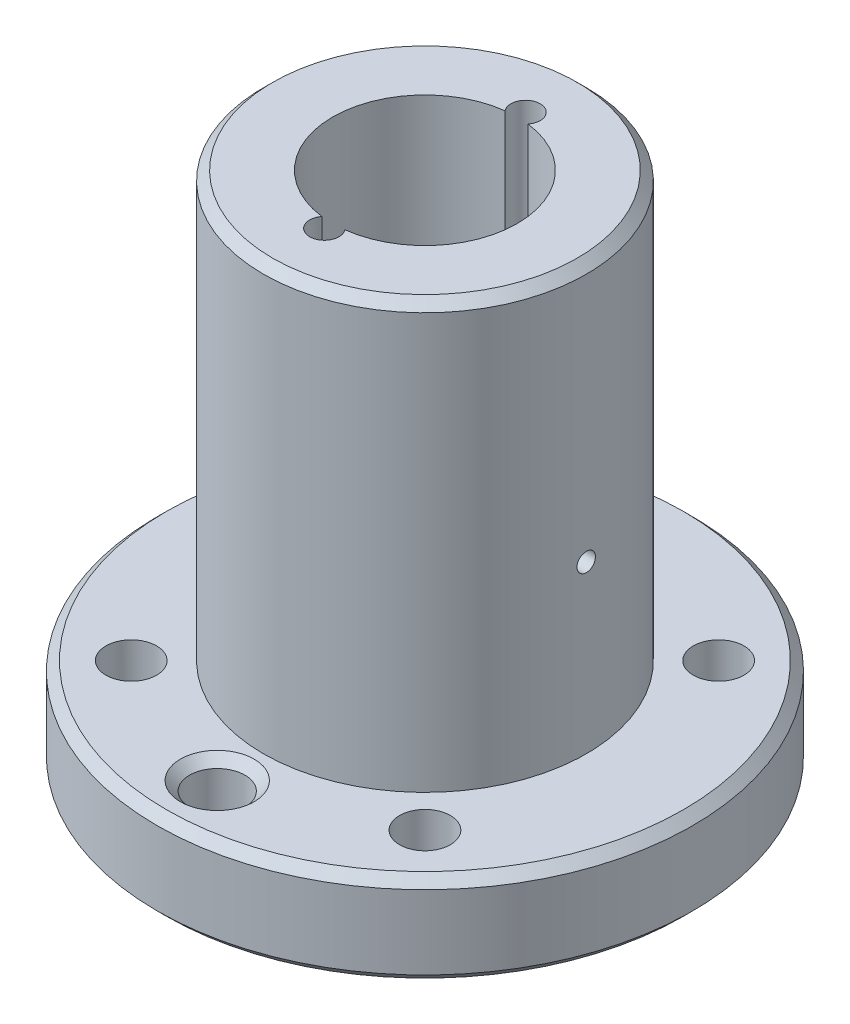
SolidWorks part; units mm, degrees
ref_plane "前视基准面" through (0, 0, 0) normal (0, 0, 1) x (1, 0, 0)
ref_plane "上视基准面" through (0, 0, 0) normal (0, 1, 0) x (1, 0, 0)
ref_plane "右视基准面" through (0, 0, 0) normal (1, 0, 0) x (0, 0, -1)
sketch "草图1" plane through (0, 0, 0) normal (0, 1, 0) x (1, 0, 0)
  circle A0 centre (0, 0) radius 29
  dimension "D1" = 58
extrude "凸台-拉伸1" add sketch "草图1" along normal blind 10 contours A0
sketch "草图2" plane through (0, 0, 0) normal (0, 1, 0) x (1, 0, 0)
  circle A0 centre (0, 0) radius 17.5
  dimension "D1" = 35
extrude "凸台-拉伸2" add sketch "草图2" along normal blind 56
sketch "草图3" plane through (0, 0, 0) normal (0, 1, 0) x (1, 0, 0)
  line L0 (-20.6924, 0) -> (25.4755, 0) construction
  line L1 (0, -13.4656) -> (0, 18.3528) construction
  circle A0 centre (0, 0) radius 10
  circle A1 centre (0, -10.9) radius 1.585
  circle A2 centre (0, 10.9) radius 1.585
  point P9 (0, -9.315)
  dimension "D1" = 20
  dimension "D2" = 9.315
  dimension "D3" = 10.9
extrude "切除-拉伸1" cut sketch "草图3" along normal up to surface (56 mm away) contours A0 up to face at (0, 56, 17.5)
sketch "草图4" plane through (0, 0, 0) normal (0, -1, 0) x (1, 0, 0)
  line L0 (-41.1768, 0) -> (51.7309, 0) construction
  line L1 (0, 31.5584) -> (0, -31.9744) construction
  line L2 (-15.9099, 15.9099) -> (0, 0) construction
  circle A0 centre (0, 0) radius 22.5 construction
  circle A1 centre (-15.9099, 15.9099) radius 4.75
  circle A2 centre (-15.9099, 15.9099) radius 2.75
  circle A3 centre (15.9099, 15.9099) radius 2.75
  circle A4 centre (15.9099, 15.9099) radius 4.75
  circle A5 centre (15.9099, -15.9099) radius 2.75
  circle A6 centre (15.9099, -15.9099) radius 4.75
  circle A7 centre (-15.9099, -15.9099) radius 2.75
  circle A8 centre (-15.9099, -15.9099) radius 4.75
  circle A9 centre (0, 22.5) radius 3
  dimension "D1" = 45
  dimension "D3" = 9.5
  dimension "D4" = 5.5
  dimension "D5" = 6
  dimension "D2" = 45
extrude "切除-拉伸2" cut sketch "草图4" against normal up to next contours A2 | A7 | A5 | A3 | A9 region at (-15.9099, 0, 15.9099) region at (15.9099, 0, 15.9099) region at (15.9099, 0, -15.9099) region at (-15.9099, 0, -15.9099) region at (0, 0, 22.5)
extrude "切除-拉伸3" cut sketch "草图4<4>" against normal blind 5.4 contours A1 A2 | A4 A3 | A6 A5 | A8 A7 region at (-20.5256, 0, 15.9099) region at (11.2943, 0, 15.9099) region at (11.2943, 0, -15.9099) region at (-20.5256, 0, -15.9099)
sketch "草图4<4>" plane through (0, 0, 0) normal (0, -1, 0) x (1, 0, 0) same geometry as "草图4"
extrude "切除-拉伸4" cut sketch "草图3<3>" along normal up to next contours A0 A1 | A2 A0 region at (0, 0, -11.1112) region at (0, 0, 11.1112)
sketch "草图3<3>" plane through (0, 0, 0) normal (0, 1, 0) x (1, 0, 0) same geometry as "草图3"
ref_plane "基准面1" through (0, 28, 0) normal (0, 1, 0) x (1, 0, 0)
ref_plane "基准面2" through (0, 24, 0) normal (0, 1, 0) x (1, 0, 0)
sketch "草图5" plane through (0, 24, 0) normal (0, 1, 0) x (1, 0, 0)
  line L0 (-36.4872, 0) -> (42.7209, 0) construction
  line L1 (0, 27.7943) -> (0, -30.5394) construction
  line L2 (15.9099, 15.9099) -> (-15.9099, -15.9099) construction
  line L3 (-15.9099, 15.9099) -> (15.9099, -15.9099) construction
  circle A0 centre (0, 0) radius 17.5 construction
  circle A1 centre (0, 0) radius 17.5 construction
  circle A2 centre (0, 0) radius 17.5 construction
  point P9 (-12.3744, 12.3744)
  point P23 (12.3744, 12.3744)
  point P26 (-12.3744, -12.3744)
  point P27 (12.3744, -12.3744)
sketch "草图6" plane through (0, 28, 0) normal (0, 1, 0) x (1, 0, 0)
  line L0 (-33.9389, 0) -> (36.0687, 0) construction
  line L2 (-36.4872, 0) -> (42.7209, 0) construction
  circle A0 centre (0, 0) radius 17.5 construction
  circle A1 centre (0, 0) radius 17.5 construction
  point P3 (-17.5, 0)
  point P4 (17.5, 0)
sketch "草图9" plane through (0, 0, 0) normal (1, 0, 0) x (0, 0, -1)
  circle A0 centre (0, 28) radius 1
  dimension "D1" = 2
extrude "切除-拉伸5" cut sketch "草图9" against normal through all both and the other way through all
sketch "草图11" plane through (0, 0, 0) normal (0, 1, 0) x (1, 0, 0)
  line L0 (15.9099, 15.9099) -> (-15.9099, -15.9099) construction
  line L1 (19.2687, -12.5511) -> (15.2686, -8.5511)
  line L2 (-36.4872, 0) -> (42.7209, 0) construction
  line L3 (12.5511, -19.2687) -> (8.5511, -15.2686)
  line L4 (12.5511, -19.2687) -> (19.2687, -12.5511)
  line L5 (0, -33.6084) -> (0, 31.7942) construction
  line L6 (-39.5862, 0) -> (54.9544, 0) construction
  line L7 (-19.2687, -12.5511) -> (-15.2686, -8.5511)
  line L8 (-12.5511, -19.2687) -> (-19.2687, -12.5511)
  line L9 (-12.5511, -19.2687) -> (-8.5511, -15.2686)
  line L10 (19.2687, 12.5511) -> (15.2686, 8.5511)
  line L11 (12.5511, 19.2687) -> (19.2687, 12.5511)
  line L12 (12.5511, 19.2687) -> (8.5511, 15.2686)
  line L13 (-12.5511, 19.2687) -> (-8.5511, 15.2686)
  line L14 (-19.2687, 12.5511) -> (-15.2686, 8.5511)
  line L15 (-12.5511, 19.2687) -> (-19.2687, 12.5511)
  circle A1 centre (15.9099, -15.9099) radius 4.75 construction
  arc A6 (8.5511, 15.2686) -> (-8.5511, 15.2686) centre (0, 0) ccw
  arc A7 (-8.5511, -15.2686) -> (8.5511, -15.2686) centre (0, 0) ccw
  arc A8 (15.2686, -8.5511) -> (15.2686, 8.5511) centre (0, 0) ccw
  arc A9 (-15.2686, 8.5511) -> (-15.2686, -8.5511) centre (0, 0) ccw
  dimension "D1" = 17.5
  dimension "D2" = 45
  dimension "D3" = 45
extrude "切除-拉伸6" cut sketch "草图11" along normal blind 5.4 contours L14 A9 L7 L8 L9 A7 L3 L4 L1 A8 L10 L11 L12 A6 L13 L15 region at (0, 0, 0)
ref_plane "基准面8" through (0, 0, 0) normal (0.7071, 0, 0.7071) x (-0.7071, 0, 0.7071)
ref_plane "基准面10" through (0, 40, 0) normal (0, 1, 0) x (1, 0, 0)
sketch "草图29" plane through (0, 40, 0) normal (0, 1, 0) x (1, 0, 0)
  line L0 (-32.5118, 0) -> (36.4741, 0) construction
  line L1 (-36.4872, 0) -> (42.7209, 0) construction
  line L2 (0, 25.6111) -> (0, -28.2537) construction
  line L3 (0, 27.7943) -> (0, -30.5394) construction
  line L4 (-15.9099, 15.9099) -> (15.9099, -15.9099) construction
  line L5 (15.9099, 15.9099) -> (-15.9099, -15.9099) construction
  circle A0 centre (0, 0) radius 17.5 construction
  circle A1 centre (0, 0) radius 17.5 construction
  point P19 (-12.3744, 12.3744)
  point P20 (12.3744, 12.3744)
  point P22 (12.3744, -12.3744)
  point P24 (-12.3744, -12.3744)
chamfer "倒角1" distance 1 angle 45 3 edges at (0, 0, 29) (0, 10, 29) (0, 56, 17.5)
chamfer "倒角2" distance 1 angle 45 1 edges at (0, 0, 19.5)
chamfer "倒角3" distance 1 angle 45 1 edges at (0, 10, 25.5)
